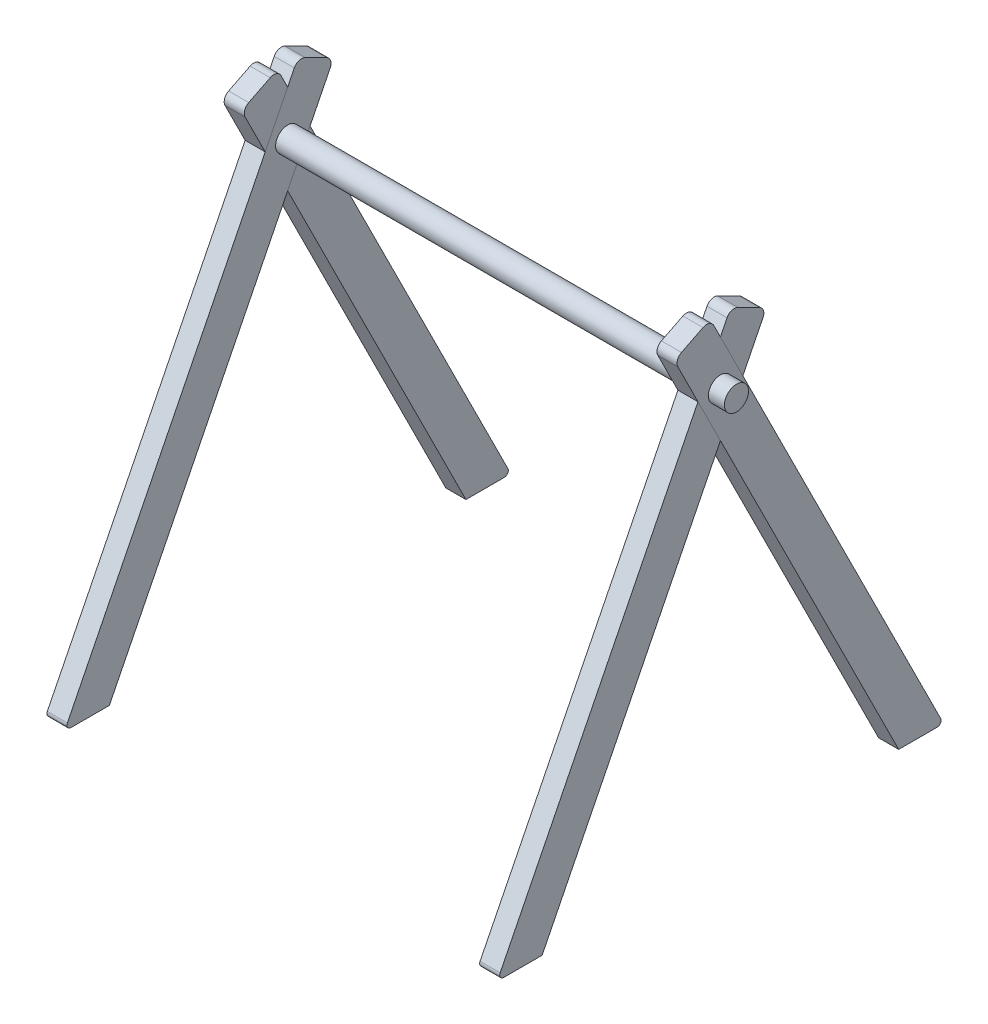
SolidWorks part; units mm, degrees
material "Pine"
ref_plane "Front Plane" through (0, 0, 0) normal (0, 0, 1) x (1, 0, 0)
ref_plane "Top Plane" through (0, 0, 0) normal (0, 1, 0) x (1, 0, 0)
ref_plane "Right Plane" through (0, 0, 0) normal (1, 0, 0) x (0, 0, -1)
sketch "Sketch1" plane through (0, 0, 0) normal (1, 0, 0) x (0, 0, -1)
  line L0 (-250, 0) -> (250, 0)
  line L1 (250, 0) -> (0, 500)
  line L2 (0, 500) -> (-250, 0)
  dimension "D1" = 500
  dimension "D2" = 500
sketch "Sketch3" plane through (0, 0, 0) normal (1, 0, 0) x (0, 0, -1)
  line L0 (-250, 0) -> (250, 0) construction
  line L1 (-402.0212, 0) -> (465.3533, 0) construction
  line L2 (12.738, 581.3777) -> (57.4593, 559.017)
  line L3 (-12.738, 581.3777) -> (-57.4593, 559.017)
  line L4 (-277.9508, 0) -> (-222.0492, 0)
  line L5 (222.0492, 0) -> (277.9508, 0)
  line L8 (-22.3607, 511.1803) -> (-272.3607, 11.1803)
  line L9 (12.738, 581.3777) -> (-277.9508, 0)
  line L10 (22.3607, 488.8197) -> (-227.6393, -11.1803)
  line L11 (57.4593, 559.017) -> (-222.0492, 0)
  line L13 (272.3607, 11.1803) -> (22.3607, 511.1803)
  line L14 (277.9508, 0) -> (-12.738, 581.3777)
  line L15 (227.6393, -11.1803) -> (-22.3607, 488.8197)
  line L16 (222.0492, 0) -> (-57.4593, 559.017)
  circle A0 centre (0, 500) radius 15
  dimension "D5" = 30
  dimension "D6" = 650
  dimension "D1" = 25
  dimension "D2" = 25
  dimension "D3" = 25
  dimension "D4" = 25
sketch "Sketch4" plane through (0, 0, 0) normal (1, 0, 0) x (0, 0, -1)
  line L0 (-277.9508, 0) -> (-222.0492, 0) construction
  line L1 (57.4593, 559.017) -> (-222.0492, 0) construction
  line L2 (12.738, 581.3777) -> (57.4593, 559.017) construction
  line L3 (12.738, 581.3777) -> (-277.9508, 0) construction
  line L4 (-277.9508, 0) -> (-222.0492, 0)
  line L5 (57.4593, 559.017) -> (-222.0492, 0)
  line L6 (12.738, 581.3777) -> (57.4593, 559.017)
  line L7 (12.738, 581.3777) -> (-277.9508, 0)
extrude "Boss-Extrude1" add sketch "Sketch4" along normal blind 25
sketch "Sketch5" plane through (0, 0, 0) normal (1, 0, 0) x (0, 0, -1)
  line L0 (-12.738, 581.3777) -> (-57.4593, 559.017) construction
  line L1 (222.0492, 0) -> (-57.4593, 559.017) construction
  line L2 (277.9508, 0) -> (-12.738, 581.3777) construction
  line L3 (222.0492, 0) -> (277.9508, 0) construction
  line L4 (222.0492, 0) -> (277.9508, 0)
  line L5 (-12.738, 581.3777) -> (-57.4593, 559.017)
  line L6 (277.9508, 0) -> (-12.738, 581.3777)
  line L7 (222.0492, 0) -> (-57.4593, 559.017)
extrude "Boss-Extrude2" add sketch "Sketch5" along normal blind 25 separate body
sketch "Sketch6" plane through (0, 0, 0) normal (-1, 0, 0) x (0, 0, 1)
  line L4 (12.738, 581.3777) -> (-277.9508, 0)
  line L5 (-277.9508, 0) -> (-222.0492, 0)
  line L6 (-222.0492, 0) -> (57.4593, 559.017)
  line L7 (57.4593, 559.017) -> (12.738, 581.3777)
  line L8 (12.738, 581.3777) -> (-277.9508, 0)
  line L9 (-277.9508, 0) -> (-222.0492, 0)
  line L10 (-222.0492, 0) -> (57.4593, 559.017)
  line L11 (57.4593, 559.017) -> (12.738, 581.3777)
  dimension "D1" = 0
extrude "Cut-Extrude1" cut sketch "Sketch6" against normal blind 12.5
sketch "Sketch7" plane through (25, 0, 0) normal (1, 0, 0) x (0, 0, -1)
  line L4 (12.738, 581.3777) -> (-277.9508, 0)
  line L5 (-277.9508, 0) -> (-222.0492, 0)
  line L6 (-222.0492, 0) -> (57.4593, 559.017)
  line L7 (57.4593, 559.017) -> (12.738, 581.3777)
  line L8 (12.738, 581.3777) -> (-277.9508, 0)
  line L9 (-277.9508, 0) -> (-222.0492, 0)
  line L10 (-222.0492, 0) -> (57.4593, 559.017)
  line L11 (57.4593, 559.017) -> (12.738, 581.3777)
  dimension "D1" = 0
extrude "Cut-Extrude2" cut sketch "Sketch7" against normal blind 12.5
sketch "Sketch8" plane through (25, 0, 0) normal (1, 0, 0) x (0, 0, -1)
  circle A0 centre (0, 500) radius 15 construction
  circle A1 centre (0, 500) radius 15
extrude "Cut-Extrude3" cut sketch "Sketch8" against normal through all
sketch "Sketch9" plane through (25, 0, 0) normal (1, 0, 0) x (0, 0, -1)
  circle A0 centre (0, 500) radius 3.25
  dimension "D1" = 6.5
extrude "Cut-Extrude4" cut sketch "Sketch9" against normal through all
fillet "Fillet1" radius 10 2 edges at (12.5, 559.017, 57.4593) (12.5, 581.3777, 12.738)
fillet "Fillet2" radius 10 2 edges at (12.5, 581.3777, -12.738) (12.5, 559.017, -57.4593)
fillet "Fillet3" radius 5 1 edges at (12.5, 0, 277.9508)
fillet "Fillet4" radius 5 1 edges at (12.5, 0, -277.9508)
ref_plane "Plane1" through (282, 0, 0) normal (1, 0, 0) x (0, 0, -1)
mirror "Mirror1" about plane through (282, 0, 0) normal (1, 0, 0) of bodies 106 107
sketch "Sketch10" plane through (12.5, 0, 0) normal (1, 0, 0) x (0, 0, -1)
  circle A0 centre (0, 500) radius 15 construction
  circle A1 centre (0, 500) radius 15
extrude "Boss-Extrude4" add sketch "Sketch10" along normal up to surface (539 mm away) separate body up to face at (551.5, 500, -3.25)
hole_wizard "M6 Tapped Hole1" positions "Sketch12" profile "Sketch14" tap size "M6" standard "ISO"
sketch "Sketch12" plane through (12.5, 0, 0) normal (-1, 0, 0) x (0, 0, 1)
  point P0 (0, 500)
sketch "Sketch14" plane through (12.5, 500, 0) normal (0, 1, 0) x (0, 0, 1)
  line L0 (0, 0) -> (0, 26.5022)
  line L1 (0, 26.5022) -> (2.5, 25)
  line L2 (2.5, 25) -> (2.5, 0)
  line L5 (2.5, 0) -> (0, 0)
  line L10 (0, 26.5022) -> (-2.5, 25) construction
  line L11 (0, -6.35) -> (0, 107.95) construction
  dimension "Tap Drill Dia." = 5
  dimension "Tap Drill Depth" = 25
  dimension "Drill Angle" = 118
cosmetic thread "Hole Thread1" parameters "D1"=22, "D2"=6
hole_wizard "M6 Tapped Hole2" positions "Sketch15" profile "Sketch16" tap size "M6" standard "ISO"
sketch "Sketch15" plane through (551.5, 0, 0) normal (1, 0, 0) x (0, 0, -1)
  point P0 (0, 500)
sketch "Sketch16" plane through (551.5, 500, 0) normal (0, 1, 0) x (0, 0, -1)
  line L0 (0, 0) -> (0, 26.5022)
  line L1 (0, 26.5022) -> (2.5, 25)
  line L2 (2.5, 25) -> (2.5, 0)
  line L5 (2.5, 0) -> (0, 0)
  line L10 (0, 26.5022) -> (-2.5, 25) construction
  line L11 (0, -6.35) -> (0, 107.95) construction
  dimension "Tap Drill Dia." = 5
  dimension "Tap Drill Depth" = 25
  dimension "Drill Angle" = 118
cosmetic thread "Hole Thread2" parameters "D1"=22, "D2"=6
sketch "Sketch17" plane through (12.5, 0, 0) normal (-1, 0, 0) x (0, 0, 1)
  circle A0 centre (0, 500) radius 3
  dimension "D1" = 6
extrude "Boss-Extrude5" add sketch "Sketch17" along normal blind 22 and the other way blind 20 separate body
mirror "Mirror3" about plane through (282, 0, 0) normal (1, 0, 0) of bodies 113
sketch "Sketch18" plane through (0, 0, 0) normal (-1, 0, 0) x (0, 0, 1)
  circle A1 centre (0, 500) radius 15 construction
  circle A2 centre (0, 500) radius 15
extrude "Boss-Extrude6" add sketch "Sketch18" along normal blind 20 separate body
sketch "Sketch19" plane through (0, 0, 0) normal (-1, 0, 0) x (0, 0, 1)
  circle A0 centre (0, 500) radius 3
  dimension "D1" = 6
extrude "Cut-Extrude5" cut sketch "Sketch19" along normal blind 10
mirror "Mirror4" about plane through (282, 0, 0) normal (1, 0, 0) of bodies 116
delete or keep bodies "Body-Delete/Keep 1" [suppressed] type delete bodies bodies 106 107 108 109 116 117
delete or keep bodies "Body-Delete/Keep 2" [suppressed] type delete bodies bodies 106 114 113 112 109 108 107 117
delete or keep bodies "Body-Delete/Keep 3" [suppressed] type delete bodies bodies 107 116 114 113 112 109 108 117
delete or keep bodies "Body-Delete/Keep 4" [suppressed] type delete bodies bodies 106 109 108 117 116 114 113 112
